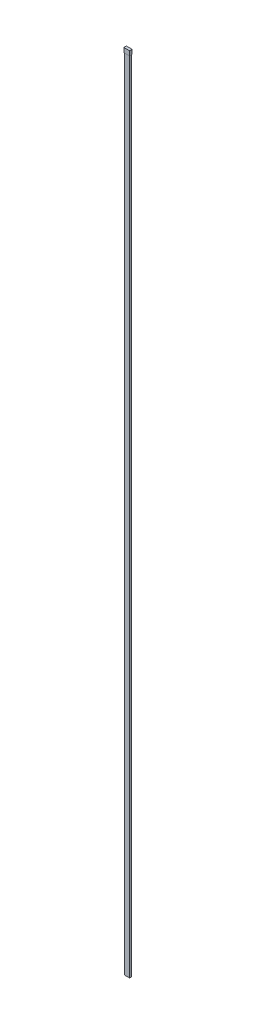
SolidWorks part; units mm, degrees
ref_plane "Front Plane" through (0, 0, 0) normal (0, 0, 1) x (1, 0, 0)
ref_plane "Top Plane" through (0, 0, 0) normal (0, 1, 0) x (1, 0, 0)
ref_plane "Right Plane" through (0, 0, 0) normal (1, 0, 0) x (0, 0, -1)
sketch "Sketch1" plane through (0, 0, 0) normal (0, 0, 1) x (1, 0, 0)
  line L1 (-7.1438, -5.5562) -> (7.1437, -5.5562)
  line L2 (-7.1438, -5.5562) -> (-7.1438, 5.5562)
  line L3 (-7.1438, 5.5562) -> (7.1437, 5.5562)
  line L4 (7.1437, -5.5562) -> (7.1437, 5.5562)
  line L5 (-7.1438, -5.5562) -> (7.1437, 5.5562) construction
  line L6 (-7.1438, 5.5562) -> (7.1437, -5.5562) construction
  point P0 (0, 0)
  point P6 (0, 0)
  dimension "D1" = 14.2875
  dimension "D2" = 11.1125
sketch "Sketch2" plane through (0, 0, 0) normal (0, 0, 1) x (1, 0, 0)
  line L0 (-7.1438, -5.5562) -> (7.1437, -5.5562) construction
  line L1 (-6.35, -1994.4437) -> (6.35, -1994.4437)
  line L2 (-6.35, -1994.4437) -> (-6.35, -5.5562)
  line L3 (-6.35, -5.5562) -> (6.35, -5.5562)
  line L4 (6.35, -1994.4437) -> (6.35, -5.5562)
  line L5 (-6.35, -1994.4437) -> (6.35, -5.5562) construction
  line L6 (-6.35, -5.5562) -> (6.35, -1994.4437) construction
  point P0 (0, -1000)
  point P7 (0, -5.5562)
  point P8 (0, -5.5562)
  dimension "D1" = 1988.8875
  dimension "D2" = 12.7
extrude "Boss-Extrude1" add sketch "Sketch2" along normal mid plane 4.7625
extrude "Boss-Extrude2" add sketch "Sketch1" along normal mid plane 6.35
equation "\"led-strip-cap-width\"= 9 / 16in"
equation "\"led-strip-cap-height\"= 7 / 16in"
equation "\"led-strip-cap-thickness\"= .25in"
equation "\"led-strip-length\"= 2m"
equation "\"led-strip-visible-length\"= \"led-strip-length\" - \"led-strip-cap-height\""
equation "\"led-strip-width\"= .5in"
equation "\"led-strip-thickness\"= 3 / 16in"
equation "\"D1@Sketch1\"=\"led-strip-cap-width\""
equation "\"D2@Sketch1\"=\"led-strip-cap-height\""
equation "\"D1@Sketch2\"=\"led-strip-visible-length\""
equation "\"D2@Sketch2\"=\"led-strip-width\""
equation "\"D1@Boss-Extrude1\"=\"led-strip-thickness\""
equation "\"D1@Boss-Extrude2\"=\"led-strip-cap-thickness\""
